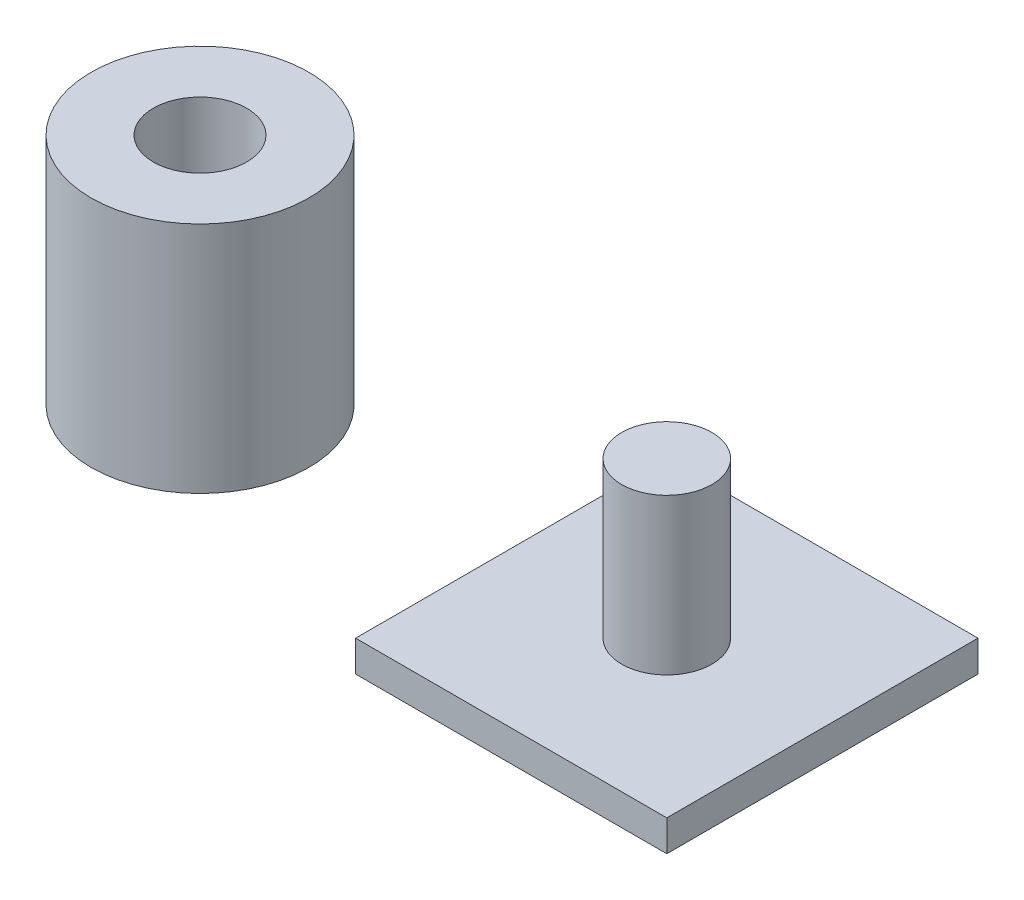
SolidWorks part; units mm, degrees
ref_plane "Front Plane" through (0, 0, 0) normal (0, 0, 1) x (1, 0, 0)
ref_plane "Top Plane" through (0, 0, 0) normal (0, 1, 0) x (1, 0, 0)
ref_plane "Right Plane" through (0, 0, 0) normal (1, 0, 0) x (0, 0, -1)
sketch "Sketch1" plane through (0, 0, 0) normal (0, 1, 0) x (1, 0, 0)
  line L1 (-10, 10) -> (10, 10)
  line L2 (-10, 10) -> (-10, -10)
  line L3 (-10, -10) -> (10, -10)
  line L4 (10, 10) -> (10, -10)
  line L5 (-10, 10) -> (10, -10) construction
  line L6 (-10, -10) -> (10, 10) construction
  circle A0 centre (0, 0) radius 2.9
  point P0 (0, 0)
  dimension "D2" = 5.8
  dimension "D1" = 20
extrude "Boss-Extrude1" add sketch "Sketch1" along normal blind 12 contours A0 region at (0, 0, 0)
extrude "Boss-Extrude2" add sketch "Sketch1<3>" along normal blind 2
sketch "Sketch1<3>" plane through (0, 0, 0) normal (0, 1, 0) x (1, 0, 0) same geometry as "Sketch1"
sketch "Sketch2" plane through (0, 0, 0) normal (0, 1, 0) x (1, 0, 0)
  circle A0 centre (-30, 0) radius 3
  circle A1 centre (-30, 0) radius 7
  point P3 (-16.2655, 0)
  point P5 (0, 0)
  dimension "D1" = 6
  dimension "D2" = 14
  dimension "D3" = 30
extrude "Boss-Extrude3" add sketch "Sketch2" along normal blind 15 separate body
